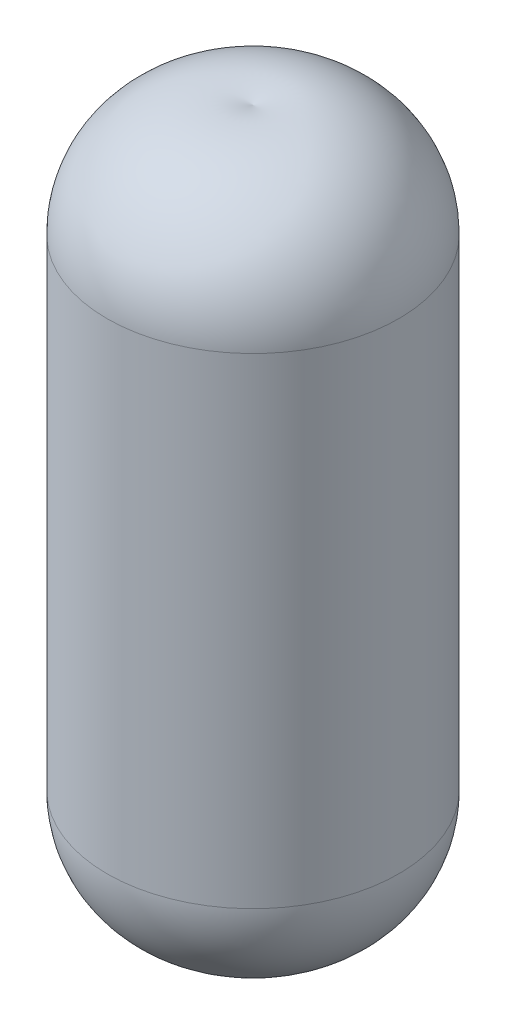
SolidWorks part; units mm, degrees
other "Markup1"
sketch "Sketch2" plane through (1062.5, -500, 1062.5) normal (0.0649, -0.0227, 0.9976) x (-0.9976, -0.0258, 0.0643)
ref_plane "Front Plane" through (0, 0, 0) normal (0, 0, 1) x (1, 0, 0)
ref_plane "Top Plane" through (0, 0, 0) normal (0, 1, 0) x (1, 0, 0)
ref_plane "Right Plane" through (0, 0, 0) normal (1, 0, 0) x (0, 0, -1)
sketch "Sketch1" plane through (0, 0, 0) normal (0, 0, 1) x (1, 0, 0)
  line L0 (0, 1509.902) -> (0, -522.098)
  line L4 (0, -522.098) -> (0, -979.298)
  line L5 (609.6, -510.637) -> (609.6, 1498.441)
  line L6 (0, 1509.902) -> (0, 1967.102)
  arc A19 (609.6, -510.637) -> (0, -979.298) centre (124.6465, -510.637) cw
  arc A20 (609.6, 1498.441) -> (0, 1967.102) centre (124.6465, 1498.441) ccw
  point P0 (0, 0)
  point P10 (0, 493.902)
  dimension "D1" = 609.6
  dimension "D2" = 2032
  dimension "D3" = 1016
  dimension "D4" = 457.2
  dimension "D5" = 457.2
ref_axis "Axis1" through (0, 550, 0) along (0, -1, 0)
revolve "Revolve2" add sketch "Sketch1" angle 360 about axis through (0, 550, 0) along (0, -1, 0)
ref_plane "Plane1" through (0, 493.902, 0) normal (0, 1, 0) x (1, 0, 0)
